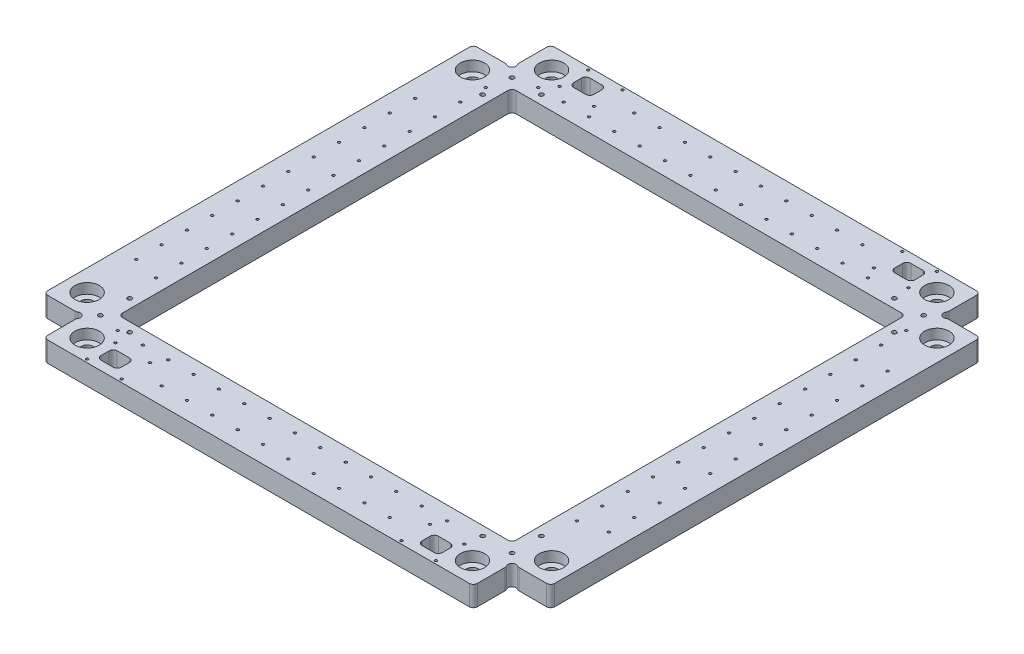
SolidWorks part; units mm, degrees
material "ASTM A36 Steel"
ref_plane "Front Plane" through (0, 0, 0) normal (0, 0, 1) x (1, 0, 0)
ref_plane "Top Plane" through (0, 0, 0) normal (0, 1, 0) x (1, 0, 0)
ref_plane "Right Plane" through (0, 0, 0) normal (1, 0, 0) x (0, 0, -1)
sketch "Sketch1" plane through (0, 0, 0) normal (0, 1, 0) x (1, 0, 0)
  line L1 (250, -250) -> (-250, -250)
  line L2 (250, -250) -> (250, 250)
  line L3 (250, 250) -> (-250, 250)
  line L4 (-250, -250) -> (-250, 250)
  line L5 (250, -250) -> (-250, 250) construction
  line L6 (250, 250) -> (-250, -250) construction
  point P0 (0, 0)
  dimension "D1" = 500
  dimension "D2" = 500
extrude "Boss-Extrude1" add sketch "Sketch1" along normal blind 20
sketch "Sketch2" plane through (0, 20, 0) normal (0, 1, 0) x (1, 0, 0)
  line L0 (250, 250) -> (-250, 250) construction
  line L10 (-250, 250) -> (-250, -250) construction
  line L15 (-250, 169) -> (-208, 169)
  line L16 (-250, 169) -> (-250, 211)
  line L17 (-174.5, 213.5) -> (-205.5, 213.5)
  line L27 (-250, 211) -> (-208, 211)
  line L33 (-208, 169) -> (-208, 211)
  line L35 (-250, 169) -> (-208, 211) construction
  line L36 (-250, 211) -> (-208, 169) construction
  line L37 (-169, 208) -> (-211, 208)
  line L38 (-169, 208) -> (-169, 250)
  line L39 (-169, 250) -> (-211, 250)
  line L40 (-211, 208) -> (-211, 250)
  line L41 (-169, 208) -> (-211, 250) construction
  line L42 (-169, 250) -> (-211, 208) construction
  line L43 (-208, 206) -> (-213, 211)
  line L44 (-174.5, 213.5) -> (-174.5, 244.5)
  line L45 (-174.5, 244.5) -> (-205.5, 244.5)
  line L46 (-205.5, 213.5) -> (-205.5, 244.5)
  line L47 (-174.5, 213.5) -> (-205.5, 244.5) construction
  line L48 (-174.5, 244.5) -> (-205.5, 213.5) construction
  line L49 (-213.5, 174.5) -> (-244.5, 174.5)
  line L50 (-213.5, 174.5) -> (-213.5, 205.5)
  line L51 (-213.5, 205.5) -> (-244.5, 205.5)
  line L52 (-244.5, 174.5) -> (-244.5, 205.5)
  line L53 (-213.5, 174.5) -> (-244.5, 205.5) construction
  line L54 (-213.5, 205.5) -> (-244.5, 174.5) construction
  line L55 (-206, 208) -> (-211, 213)
  line L56 (-213, 211) -> (-211, 213) construction
  point P1 (-229, 190)
  point P5 (-190, 229)
  point P23 (-229, 190)
  point P27 (-190, 229)
  dimension "D1" = 5
  dimension "D2" = 45
  dimension "D3" = 42
  dimension "D4" = 31
  dimension "D5" = 45
  dimension "D6" = 5
  dimension "D7" = 60
hole_wizard "Bearing Press Fit" positions "Sketch8" profile "Sketch9" hole size "Ø11.8" standard "ANSI Metric" end condition through all
sketch "Sketch8" plane through (0, 20, 0) normal (0, 1, 0) x (1, 0, 0)
  line L1 (-169, 250) -> (-211, 208) construction
  point P8 (-190, 229)
  point P12 (-229, 190)
sketch "Sketch9" plane through (-190, 20, -229) normal (1, 0, 0) x (0, 0, 1)
  line L0 (0, 0) -> (0, 20)
  line L1 (0, 20) -> (5.9, 20)
  line L2 (5.9, 20) -> (5.9, 0)
  line L5 (5.9, 0) -> (0, 0)
  line L11 (0, -6.35) -> (0, 107.95) construction
  dimension "Thru Hole Dia." = 11.8
  dimension "Thru Hole Depth" = 20
ref_axis "Axis1" through (0, 21, 0) along (0, -1, 0)
pattern_circular "CirPattern1" count 4 over 360 about axis through (0, 21, 0) along (0, -1, 0) of "Bearing Press Fit"
sketch "Sketch5" plane through (0, 20, 0) normal (0, 1, 0) x (1, 0, 0)
  line L1 (194, -194) -> (-194, -194)
  line L2 (194, -194) -> (194, 194)
  line L3 (194, 194) -> (-194, 194)
  line L4 (-194, -194) -> (-194, 194)
  line L5 (194, -194) -> (-194, 194) construction
  line L6 (194, 194) -> (-194, -194) construction
  point P0 (0, 0)
  dimension "D1" = 388
extrude "Cut-Extrude1" cut sketch "Sketch5" against normal up to surface (20 mm away) up to face at (-229, 0, 195.9)
sketch "Sketch10" plane through (0, 0, 0) normal (0, 1, 0) x (1, 0, 0)
  line L5 (194, 194) -> (-194, 194) construction
  line L6 (214, -214) -> (-214, -214)
  line L14 (214, -214) -> (214, 214)
  line L15 (214, 214) -> (-214, 214)
  line L16 (-214, -214) -> (-214, 214)
  line L17 (214, -214) -> (-214, 214) construction
  line L18 (214, 214) -> (-214, -214) construction
  line L19 (201.5, -201.5) -> (-201.5, -201.5)
  line L20 (201.5, -201.5) -> (201.5, 201.5)
  line L21 (201.5, 201.5) -> (-201.5, 201.5)
  line L22 (-201.5, -201.5) -> (-201.5, 201.5)
  line L23 (201.5, -201.5) -> (-201.5, 201.5) construction
  line L24 (201.5, 201.5) -> (-201.5, -201.5) construction
  point P0 (0, 0)
  point P6 (0, 0)
  dimension "D2" = 7.5
  dimension "D1" = 12.5
extrude "Linear Rail Slot" cut sketch "Sketch10" along normal blind 2.5
fillet "Fillet2" radius 4 4 edges at (-194, 10, 194) (194, 10, 194) (194, 10, -194) (-194, 10, -194)
sketch "Sketch11" plane through (0, 2.5, 0) normal (0, -1, 0) x (1, 0, 0)
  line L0 (-204, 207.5) -> (156, 207.5)
  line L1 (-201.5, 201.5) -> (201.5, 201.5) construction
  line L3 (-214, -214) -> (-214, 214) construction
  point P16 (143.5, 207.5)
  point P18 (118.5, 207.5)
  point P19 (93.5, 207.5)
  point P20 (68.5, 207.5)
  point P21 (43.5, 207.5)
  point P22 (18.5, 207.5)
  point P23 (-6.5, 207.5)
  point P24 (-31.5, 207.5)
  point P25 (-56.5, 207.5)
  point P26 (-81.5, 207.5)
  point P28 (-106.5, 207.5)
  point P29 (-131.5, 207.5)
  point P30 (-156.5, 207.5)
  point P31 (-181.5, 207.5)
  dimension "D1" = 360
  dimension "D2" = 6
  dimension "D4" = 14
  dimension "D5" = 25
  dimension "D6" = 10
  dimension "D3" = 12.5
hole_wizard "Tap Drill for M3x0.5 Tap1" positions "Sketch12" profile "Sketch13" hole size "M3x0.5" standard "ANSI Metric" end condition through all
sketch "Sketch12" plane through (0, 2.5, 0) normal (0, -1, 0) x (-1, 0, 0)
  line L0 (204, -207.5) -> (-156, -207.5) construction
  point P28 (-143.5, -207.5)
  point P31 (-118.5, -207.5)
  point P34 (-93.5, -207.5)
  point P37 (-68.5, -207.5)
  point P40 (-43.5, -207.5)
  point P43 (-18.5, -207.5)
  point P46 (6.5, -207.5)
  point P49 (31.5, -207.5)
  point P51 (56.5, -207.5)
  point P54 (81.5, -207.5)
  point P57 (106.5, -207.5)
  point P61 (131.5, -207.5)
  point P64 (156.5, -207.5)
  point P67 (181.5, -207.5)
sketch "Sketch13" plane through (143.5, 2.5, 207.5) normal (1, 0, 0) x (0, 0, -1)
  line L0 (0, 0) -> (0, 17.5)
  line L1 (0, 17.5) -> (1.25, 17.5)
  line L2 (1.25, 17.5) -> (1.25, 0)
  line L5 (1.25, 0) -> (0, 0)
  line L11 (0, -6.35) -> (0, 107.95) construction
  dimension "Thru Hole Dia." = 2.5
  dimension "Thru Hole Depth" = 17.5
sketch "Sketch14" plane through (0, 0, 0) normal (0, -1, 0) x (1, 0, 0)
  line L1 (-156.5, 213.5) -> (-181.5, 213.5)
  line L2 (-152.5, 217.5) -> (-152.5, 219.5)
  line L3 (-156.5, 223.5) -> (-181.5, 223.5)
  line L4 (-185.5, 217.5) -> (-185.5, 219.5)
  line L5 (-152.5, 213.5) -> (-185.5, 223.5) construction
  line L6 (-152.5, 223.5) -> (-185.5, 213.5) construction
  line L7 (-201.5, 201.5) -> (201.5, 201.5) construction
  line L8 (-181.5, 207.5) -> (-156.5, 207.5) construction
  line L19 (-6.5, 213.5) -> (-31.5, 213.5)
  line L25 (-2.5, 217.5) -> (-2.5, 219.5)
  line L26 (-6.5, 223.5) -> (-31.5, 223.5)
  line L31 (-35.5, 217.5) -> (-35.5, 219.5)
  line L32 (-2.5, 213.5) -> (-35.5, 223.5) construction
  line L33 (-2.5, 223.5) -> (-35.5, 213.5) construction
  line L34 (-31.5, 207.5) -> (-6.5, 207.5) construction
  line L35 (143.5, 213.5) -> (118.5, 213.5)
  line L36 (147.5, 217.5) -> (147.5, 219.5)
  line L37 (143.5, 223.5) -> (118.5, 223.5)
  line L38 (114.5, 217.5) -> (114.5, 219.5)
  line L39 (147.5, 213.5) -> (114.5, 223.5) construction
  line L40 (147.5, 223.5) -> (114.5, 213.5) construction
  line L41 (118.5, 207.5) -> (143.5, 207.5) construction
  arc A3 (-152.5, 219.5) -> (-156.5, 223.5) centre (-156.5, 219.5) ccw
  arc A4 (-156.5, 213.5) -> (-152.5, 217.5) centre (-156.5, 217.5) ccw
  arc A5 (-181.5, 213.5) -> (-185.5, 217.5) centre (-181.5, 217.5) cw
  arc A6 (-181.5, 223.5) -> (-185.5, 219.5) centre (-181.5, 219.5) ccw
  arc A7 (-2.5, 219.5) -> (-6.5, 223.5) centre (-6.5, 219.5) ccw
  arc A8 (-6.5, 213.5) -> (-2.5, 217.5) centre (-6.5, 217.5) ccw
  arc A9 (-31.5, 213.5) -> (-35.5, 217.5) centre (-31.5, 217.5) cw
  arc A10 (-31.5, 223.5) -> (-35.5, 219.5) centre (-31.5, 219.5) ccw
  arc A11 (147.5, 219.5) -> (143.5, 223.5) centre (143.5, 219.5) ccw
  arc A12 (143.5, 213.5) -> (147.5, 217.5) centre (143.5, 217.5) ccw
  arc A13 (118.5, 213.5) -> (114.5, 217.5) centre (118.5, 217.5) cw
  arc A14 (118.5, 223.5) -> (114.5, 219.5) centre (118.5, 219.5) ccw
  point P0 (-169, 218.5)
  point P12 (-169, 207.5)
  point P26 (-19, 218.5)
  point P45 (131, 218.5)
  dimension "D5" = 3
  dimension "D4" = 4
  dimension "D1" = 33
  dimension "D2" = 12
  dimension "D3" = 10
  dimension "D7" = 25
  dimension "D6" = 150
mirror "Mirror5" about plane through (0, 0, 0) normal (0, 0, 1) of "Tap Drill for M3x0.5 Tap1"
ref_plane "Plane1" through (0, 0, 0) normal (-0.7071, 0, 0.7071) x (0.7071, 0, 0.7071)
mirror "Mirror6" about plane through (0, 0, 0) normal (-0.7071, 0, 0.7071) of "Mirror5"
sketch "Sketch19" plane through (0, 2.5, 0) normal (0, -1, 0) x (1, 0, 0)
  line L0 (-198.5, 201.5) -> (-198.5, 214)
  line L1 (-201.5, 201.5) -> (201.5, 201.5) construction
  line L2 (-214, 214) -> (214, 214) construction
  line L3 (-198.5, 214) -> (-214, 214)
  line L4 (-214, 214) -> (-214, 198.5)
  line L5 (-214, -214) -> (-214, 214) construction
  line L6 (-214, 198.5) -> (-201.5, 198.5)
  line L7 (-201.5, -201.5) -> (-201.5, 201.5) construction
  line L8 (-201.5, 198.5) -> (-201.5, 201.5)
  line L9 (-201.5, 201.5) -> (-198.5, 201.5)
  dimension "D1" = 3
extrude "Boss-Extrude2" add sketch "Sketch19" along normal up to surface (2.5 mm away) up to face at (-229, 0, 195.9)
pattern_circular "CirPattern4" count 4 over 360 about axis through (0, 21, 0) along (0, -1, 0) of "Boss-Extrude2"
sketch "Sketch20" plane through (0, 20, 0) normal (0, 1, 0) x (1, 0, 0)
  line L5 (-250, -250) -> (250, -250) construction
  line L20 (148.3, -225) -> (168.3, -241) construction
  line L23 (168.3, -225) -> (148.3, -241) construction
  line L28 (122, -247) -> (172, -219) construction
  line L29 (172, -247) -> (122, -219) construction
  line L30 (172, -219) -> (122, -219) construction
  line L31 (122, -247) -> (122, -219) construction
  line L32 (172, -247) -> (122, -247) construction
  line L33 (172, -247) -> (172, -219) construction
  line L34 (164.3, -241) -> (152.3, -241)
  line L35 (148.3, -229) -> (148.3, -237)
  line L36 (164.3, -225) -> (152.3, -225)
  line L37 (168.3, -229) -> (168.3, -237)
  arc A12 (152.3, -225) -> (148.3, -229) centre (152.3, -229) ccw
  arc A13 (148.3, -237) -> (152.3, -241) centre (152.3, -237) ccw
  arc A14 (168.3, -237) -> (164.3, -241) centre (164.3, -237) cw
  arc A15 (168.3, -229) -> (164.3, -225) centre (164.3, -229) ccw
  circle A16 centre (190, -229) radius 5.9 construction
  point P65 (158.3, -233)
  point P66 (147, -233)
  point P67 (158.3, -233)
  dimension "D7" = 31.7
  dimension "D8" = 11.3
  dimension "D6" = 4
  dimension "D1" = 28
  dimension "D2" = 50
  dimension "D3" = 17
  dimension "D4" = 20
  dimension "D5" = 16
extrude "Cut-Extrude3" cut sketch "Sketch20" against normal through all
hole_wizard "Tap Drill for M3x0.5 Tap6" positions "Sketch39" profile "Sketch40" hole size "M3x0.5" standard "ANSI Metric" end condition through all
sketch "Sketch39" plane through (0, 20, 0) normal (0, 1, 0) x (1, 0, 0)
  line L1 (172, -247) -> (138, -247)
  line L2 (172, -247) -> (172, -219)
  line L3 (172, -219) -> (138, -219)
  line L4 (138, -247) -> (138, -219)
  line L5 (-250, -250) -> (250, -250) construction
  circle A0 centre (190, -229) radius 5.9 construction
  point P1 (172, -247)
  point P2 (138, -219)
  point P99 (172, -219)
  point P100 (138, -247)
  dimension "D1" = 34
  dimension "D2" = 28
  dimension "D3" = 3
  dimension "D4" = 18
sketch "Sketch40" plane through (172, 20, 247) normal (1, 0, 0) x (0, 0, 1)
  line L0 (0, 0) -> (0, 20)
  line L1 (0, 20) -> (1.25, 20)
  line L2 (1.25, 20) -> (1.25, 0)
  line L5 (1.25, 0) -> (0, 0)
  line L11 (0, -6.35) -> (0, 107.95) construction
  dimension "Thru Hole Dia." = 2.5
  dimension "Thru Hole Depth" = 20
mirror "Mirror8" about plane through (0, 0, 0) normal (1, 0, 0) of "Tap Drill for M3x0.5 Tap6", "Cut-Extrude3"
mirror "Mirror9" about plane through (0, 0, 0) normal (0, 0, 1) of "Mirror8"
sketch "Sketch27" plane through (0, 20, 0) normal (0, 1, 0) x (1, 0, 0)
  line L1 (250, -250) -> (211.9, -250)
  line L2 (250, -250) -> (250, -211.9)
  line L3 (250, -211.9) -> (211.9, -211.9)
  line L4 (211.9, -250) -> (211.9, -211.9)
  dimension "D1" = 38.1
extrude "Cut-Extrude4" cut sketch "Sketch27" against normal up to surface (20 mm away) up to face at (172, 0, -245.75)
sketch "Sketch47" plane through (0, 0, 0) normal (0, -1, 0) x (1, 0, 0)
  line L0 (211.9, 211.9) -> (214.7284, 214.7284) construction
  line L1 (211.9, 211.9) -> (250, 211.9) construction
  circle A0 centre (214.7284, 214.7284) radius 4
  dimension "D1" = 8
  dimension "D2" = 45
extrude "Cut-Extrude5" cut sketch "Sketch47" against normal up to surface (20 mm away) up to face at (70.6333, 20, 70.6333)
hole_wizard "Tap Drill for M5x0.8 Tap1" positions "Sketch50" profile "Sketch49" hole size "M5x0.8" standard "ANSI Metric"
sketch "Sketch50" plane through (0, 20, 0) normal (0, 1, 0) x (1, 0, 0)
  line L0 (250, -211.9) -> (250, 250) construction
  line L1 (-250, -250) -> (211.9, -250) construction
  line L2 (174, -203) -> (203, -203) construction
  line L3 (203, -203) -> (203, -174) construction
  point P0 (174, -203)
  point P2 (203, -203)
  point P4 (203, -174)
  dimension "D1" = 47
  dimension "D2" = 29
  dimension "D3" = 47
sketch "Sketch49" plane through (174, 20, 203) normal (1, 0, 0) x (0, 0, 1)
  line L0 (0, 0) -> (0, 11.2618)
  line L1 (0, 11.2618) -> (2.1, 10)
  line L2 (2.1, 10) -> (2.1, 0)
  line L5 (2.1, 0) -> (0, 0)
  line L10 (0, 11.2618) -> (-2.1, 10) construction
  line L11 (0, -6.35) -> (0, 107.95) construction
  dimension "Hole Dia." = 4.2
  dimension "Hole Depth" = 10
  dimension "Drill Angle" = 118
sketch "Sketch53" plane through (0, 0, 0) normal (0, -1, 0) x (1, 0, 0)
  line L0 (-148.3, 233) -> (148.3, 233) construction
  line L1 (-148.3, 229) -> (-148.3, 237) construction
  line L2 (148.3, 229) -> (148.3, 237) construction
  line L3 (-112.5, 233) -> (-168.3, 233) construction
  line L4 (-168.3, 237) -> (-168.3, 229) construction
  line L5 (112.5, 233) -> (168.3, 233) construction
  line L6 (168.3, 237) -> (168.3, 229) construction
  point P6 (-112.5, 233)
  point P7 (-87.5, 233)
  point P9 (-62.5, 233)
  point P10 (-37.5, 233)
  point P11 (-12.5, 233)
  point P12 (12.5, 233)
  point P13 (37.5, 233)
  point P14 (62.5, 233)
  point P15 (87.5, 233)
  point P16 (112.5, 233)
  point P17 (112.7627, 233)
  point P25 (0, 0)
  point P26 (137.5, 233)
  dimension "D3" = 25
  dimension "D2" = 11
hole_wizard "Tap Drill for M3x0.5 Tap7" positions "Sketch54" profile "Sketch56" hole size "M3x0.5" standard "ANSI Metric" end condition through all
sketch "Sketch54" plane through (0, 0, 0) normal (0, -1, 0) x (-1, 0, 0)
  point P0 (-112.5, -233)
  point P3 (-87.5, -233)
  point P6 (-62.5, -233)
  point P9 (-37.5, -233)
  point P12 (-12.5, -233)
  point P15 (12.5, -233)
  point P18 (37.5, -233)
  point P21 (62.5, -233)
  point P24 (87.5, -233)
  point P27 (112.5, -233)
sketch "Sketch56" plane through (112.5, 0, 233) normal (1, 0, 0) x (0, 0, -1)
  line L0 (0, 0) -> (0, 20)
  line L1 (0, 20) -> (1.25, 20)
  line L2 (1.25, 20) -> (1.25, 0)
  line L5 (1.25, 0) -> (0, 0)
  line L11 (0, -6.35) -> (0, 107.95) construction
  dimension "Thru Hole Dia." = 2.5
  dimension "Thru Hole Depth" = 20
pattern_circular "CirPattern3" count 4 over 360 about axis through (0, 21, 0) along (0, -1, 0) of "Cut-Extrude4", "Cut-Extrude5", "Tap Drill for M5x0.8 Tap1", "Tap Drill for M3x0.5 Tap7"
fillet "Fillet5" radius 4 16 edges at (198.5, 1.25, 214) (198.5, 1.25, 201.5) (201.5, 1.25, 198.5) (214, 1.25, 198.5) (-214, 1.25, 198.5) (-198.5, 1.25, 214) (-201.5, 1.25, 198.5) (-198.5, 1.25, 201.5) (-214, 1.25, -198.5) (-198.5, 1.25, -214) (-198.5, 1.25, -201.5) (-201.5, 1.25, -198.5) (198.5, 1.25, -201.5) (198.5, 1.25, -214) (201.5, 1.25, -198.5) (214, 1.25, -198.5)
hole_wizard "Ø24.0 (24) Diameter Hole1" positions "Sketch41" profile "Sketch42" hole size "Ø24.0" standard "ANSI Metric"
sketch "Sketch41" plane through (0, 20, 0) normal (0, 1, 0) x (1, 0, 0)
  point P0 (-229, -190)
  point P3 (-190, -229)
  point P6 (190, -229)
  point P9 (229, -190)
  point P12 (229, 190)
  point P15 (190, 229)
  point P18 (-190, 229)
  point P21 (-229, 190)
sketch "Sketch42" plane through (-229, 20, 190) normal (1, 0, 0) x (0, 0, 1)
  line L0 (0, 0) -> (0, 10)
  line L1 (0, 10) -> (12, 10)
  line L2 (12, 10) -> (12, 0)
  line L5 (12, 0) -> (0, 0)
  line L10 (0, 10) -> (-12, 10) construction
  line L11 (0, -6.35) -> (0, 107.95) construction
  dimension "Hole Dia." = 24
  dimension "Hole Depth" = 10
  dimension "Drill Angle" = 180
fillet "Fillet6" radius 4 16 edges at (250, 10, -211.9) (211.9, 10, -250) (-211.9, 10, -250) (-250, 10, -211.9) (211.9, 10, 250) (250, 10, 211.9) (-211.9, 10, 250) (-250, 10, 211.9) (-217.5569, 10, 211.9) (-217.5569, 10, -211.9) (-211.9, 10, -217.5569) (211.9, 10, -217.5569) (217.5569, 10, -211.9) (211.9, 10, 217.5569) (-211.9, 10, 217.5569) (217.5569, 10, 211.9)
hole_wizard "Tap Drill for M3x0.5 Tap8" positions "Sketch57" profile "Sketch58" hole size "M3x0.5" standard "ANSI Metric" end condition through all
sketch "Sketch57" plane through (0, 0, 0) normal (0, -1, 0) x (-1, 0, 0)
  line L1 (-233, -137.5) -> (233, -137.5)
  line L2 (-233, -137.5) -> (-233, 137.5)
  line L3 (-233, 137.5) -> (233, 137.5)
  line L4 (233, -137.5) -> (233, 137.5)
  line L5 (-233, -137.5) -> (233, 137.5) construction
  circle A1 centre (233, 112.5) radius 1.25 construction
  point P0 (-233, 137.5)
  point P2 (233, 137.5)
  point P4 (233, -137.5)
  point P6 (-233, -137.5)
  point P111 (0, 0)
  point P117 (-233, 62.5)
  dimension "D1" = 25
sketch "Sketch58" plane through (233, 0, -137.5) normal (1, 0, 0) x (0, 0, -1)
  line L0 (0, 0) -> (0, 20)
  line L1 (0, 20) -> (1.25, 20)
  line L2 (1.25, 20) -> (1.25, 0)
  line L5 (1.25, 0) -> (0, 0)
  line L11 (0, -6.35) -> (0, 107.95) construction
  dimension "Thru Hole Dia." = 2.5
  dimension "Thru Hole Depth" = 20
